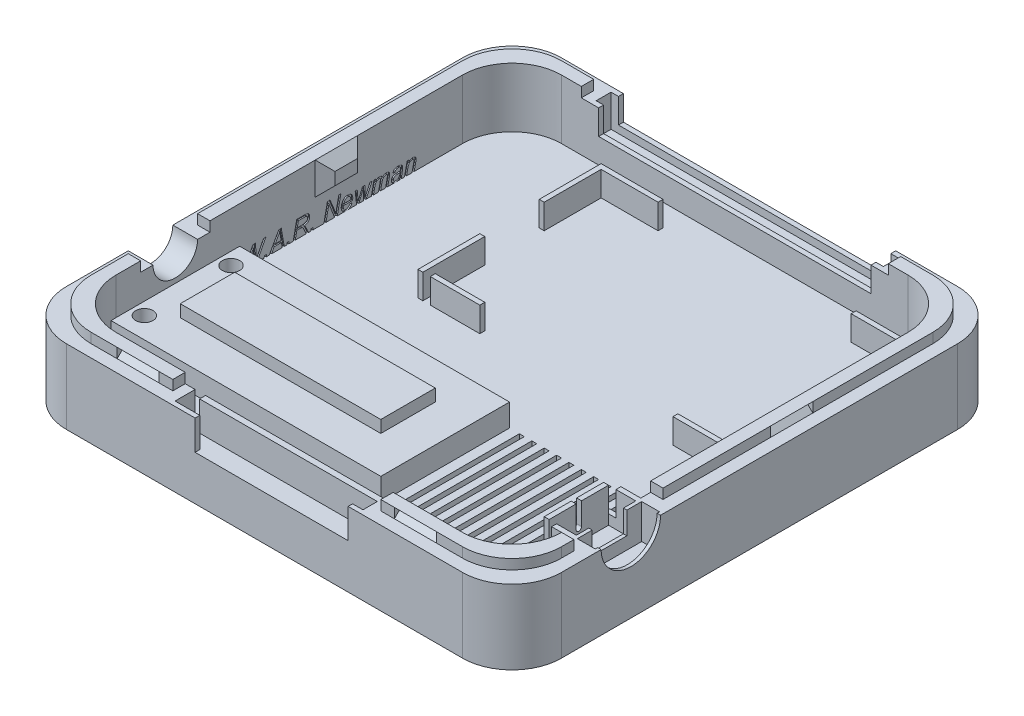
SolidWorks part; units mm, degrees
material "ABS"
ref_plane "Front Plane" through (0, 0, 0) normal (0, 0, 1) x (1, 0, 0)
ref_plane "Top Plane" through (0, 0, 0) normal (0, 1, 0) x (1, 0, 0)
ref_plane "Right Plane" through (0, 0, 0) normal (1, 0, 0) x (0, 0, -1)
sketch "Sketch1" plane through (0, 0, 0) normal (0, 1, 0) x (1, 0, 0)
  line L1 (10, 0) -> (90, 0)
  line L2 (0, 10) -> (0, 90)
  line L3 (10, 100) -> (90, 100)
  line L4 (100, 10) -> (100, 90)
  line L5 (15, 95) -> (85, 95)
  line L6 (5, 85) -> (5, 15)
  line L7 (15, 5) -> (85, 5)
  line L8 (95, 85) -> (95, 15)
  arc A0 (90, 100) -> (100, 90) centre (90, 90) cw
  arc A1 (100, 10) -> (90, 0) centre (90, 10) cw
  arc A2 (10, 0) -> (0, 10) centre (10, 10) cw
  arc A3 (0, 90) -> (10, 100) centre (10, 90) cw
  arc A4 (85, 95) -> (95, 85) centre (85, 85) cw
  arc A5 (95, 15) -> (85, 5) centre (85, 15) cw
  arc A6 (15, 5) -> (5, 15) centre (15, 15) cw
  arc A7 (5, 85) -> (15, 95) centre (15, 85) cw
  point P11 (0, 0)
  dimension "D1" = 10
  dimension "D2" = 10
extrude "Boss-Extrude1" add sketch "Sketch1" along normal blind 15
sketch "Sketch2" plane through (0, 0, 0) normal (0, 1, 0) x (1, 0, 0)
  line L1 (15, 95) -> (85, 95)
  line L2 (5, 85) -> (5, 15)
  line L3 (15, 5) -> (85, 5)
  line L4 (95, 85) -> (95, 15)
  arc A0 (85, 95) -> (95, 85) centre (85, 85) cw
  arc A1 (95, 15) -> (85, 5) centre (85, 15) cw
  arc A2 (15, 5) -> (5, 15) centre (15, 15) cw
  arc A3 (5, 85) -> (15, 95) centre (15, 85) cw
  dimension "D1" = 10
extrude "Boss-Extrude2" add sketch "Sketch2" along normal blind 5
sketch "Sketch5" plane through (0, 0, 0) normal (1, 0, 0) x (0, 0, -1)
  line L0 (15, 15) -> (27, 15)
  line L1 (85, 15) -> (15, 15) construction
  circle A0 centre (27, 15) radius 4.5
extrude "Cut-Extrude2" cut sketch "Sketch5" along normal blind 5 contours A0 region at (0, 10.6273, -27)
ref_plane "Plane1" through (0, 15, 0) normal (0, 1, 0) x (1, 0, 0)
ref_plane "Plane2" through (27.2, 0, 0) normal (1, 0, 0) x (0, 0, -1)
ref_plane "Plane3" through (0, 0, -5) normal (0, 0, 1) x (1, 0, 0)
ref_plane "Plane4" through (10, 0, 0) normal (1, 0, 0) x (0, 0, -1)
ref_plane "Plane5" through (0, 0, -10) normal (0, 0, 1) x (1, 0, 0)
ref_plane "Plane6" through (10, 0, -10) normal (-0.7071, 0, 0.7071) x (0.7071, 0, 0.7071)
ref_plane "Plane7" through (0, 0, -90) normal (0, 0, 1) x (1, 0, 0)
ref_plane "Plane8" through (-40, 0, -40) normal (0.7071, 0, 0.7071) x (0.7071, 0, -0.7071)
ref_plane "Plane9" through (90, 0, 0) normal (1, 0, 0) x (0, 0, -1)
ref_plane "Plane10" through (40, 0, 40) normal (0.7071, 0, 0.7071) x (0.7071, 0, -0.7071)
ref_plane "Plane11" through (90, 0, -90) normal (-0.7071, 0, 0.7071) x (0.7071, 0, 0.7071)
sketch "Sketch21" plane through (0, 0, 0) normal (0, 1, 0) x (1, 0, 0)
  line L0 (5, 27) -> (5, 40)
  line L1 (5, 22.5) -> (5, 31.5) construction
  line L2 (5, 85) -> (5, 15) construction
  line L3 (5, 27) -> (5, 14)
  line L4 (5, 40) -> (59.5, 40)
  line L5 (59.5, 40) -> (59.5, 14)
  line L6 (59.5, 14) -> (5, 14)
extrude "Boss-Extrude3" add sketch "Sketch21" along normal blind 9.55
sketch "Sketch22" plane through (0, 0, 0) normal (0, 1, 0) x (1, 0, 0)
  line L16 (28, 78) -> (28.5, 78)
  line L17 (40, 90) -> (40, 89.5)
  line L18 (40, 90) -> (40, 90.5)
  line L19 (28, 78) -> (27.5, 78)
  line L20 (27.5, 78) -> (27.5, 90.5)
  line L21 (27.5, 90.5) -> (40, 90.5)
  line L22 (40, 89.5) -> (28.5, 89.5)
  line L23 (28.5, 89.5) -> (28.5, 78)
  line L24 (91, 78) -> (90.5, 78)
  line L25 (91, 78) -> (91.5, 78)
  line L26 (79, 90) -> (79, 89.5)
  line L27 (79, 90) -> (79, 90.5)
  line L36 (28.5, 66) -> (28.5, 55.5)
  line L38 (27.5, 66) -> (27.5, 54.5)
  line L40 (90.5, 66) -> (90.5, 55.5)
  line L42 (91.5, 66) -> (91.5, 54.5)
  line L43 (90.5, 54.5) -> (79, 54.5)
  line L44 (79, 90.5) -> (91.5, 90.5)
  line L45 (91.5, 90.5) -> (91.5, 78)
  line L46 (90.5, 78) -> (90.5, 89.5)
  line L47 (90.5, 89.5) -> (79, 89.5)
  line L48 (28.5, 55.5) -> (28.5, 54.5)
  line L52 (30, 54.5) -> (40, 54.5)
  line L53 (27.5, 54.5) -> (27.5, 53.5)
  line L54 (27.5, 53.5) -> (28.5, 53.5)
  line L55 (28.5, 53.5) -> (28.5, 54.5)
  line L56 (30, 53.5) -> (40, 53.5)
  line L57 (27.5, 66) -> (28.5, 66)
  line L58 (40, 53.5) -> (40, 54.5)
  line L59 (79, 54.5) -> (79, 53.5)
  line L60 (30, 54.5) -> (30, 53.5)
  line L61 (79, 53.5) -> (91.5, 53.5)
  line L62 (91.5, 53.5) -> (91.5, 54.5)
  line L63 (90.5, 55.5) -> (90.5, 54.5)
  line L64 (90.5, 66) -> (91.5, 66)
extrude "Boss-Extrude4" add sketch "Sketch22" along normal blind 10
ref_plane "Plane12" through (0, 15, 0) normal (0, 1, 0) x (1, 0, 0)
ref_plane "Plane15" through (96, 0, 0) normal (1, 0, 0) x (0, 0, -1)
sketch "Sketch26" plane through (96, 0, 0) normal (1, 0, 0) x (0, 0, -1)
  line L1 (15, 15) -> (85, 15) construction
  line L2 (18, 15) -> (30, 15)
  line L3 (30, 15) -> (30, 8)
  line L4 (30, 8) -> (18, 8)
  line L5 (18, 8) -> (18, 15)
extrude "Cut-Extrude20" cut sketch "Sketch26" along normal blind 3.3
ref_plane "Plane16" through (100, 0, 0) normal (1, 0, 0) x (0, 0, -1)
sketch "Sketch29" plane through (100, 0, 0) normal (1, 0, 0) x (0, 0, -1)
  line L1 (30, 15) -> (18, 15) construction
  circle A0 centre (24, 15) radius 6
extrude "Cut-Extrude21" cut sketch "Sketch29" against normal blind 1
ref_plane "Plane17" through (95, 0, 0) normal (1, 0, 0) x (0, 0, -1)
sketch "Sketch30" plane through (95, 0, 0) normal (1, 0, 0) x (0, 0, -1)
  line L0 (30, 13) -> (30, 15)
  line L1 (15, 15) -> (85, 15) construction
  line L2 (18, 15) -> (30, 15)
  line L7 (30, 11.5) -> (30, 13)
  line L10 (30.5, 11.5) -> (30, 11.5)
  line L13 (17.5, 13) -> (17.5, 12)
  line L15 (30.5, 15) -> (30, 15)
  line L16 (17.5, 13) -> (17.5, 15)
  line L17 (17.5, 15) -> (18, 15)
  line L19 (30.5, 11.5) -> (30.5, 15)
  line L20 (18, 15) -> (18, 11.5)
  line L21 (18, 11.5) -> (17.5, 11.5)
  line L22 (17.5, 11.5) -> (17.5, 12)
  circle A0 centre (24, 10.3) radius 0.5
extrude "Cut-Extrude23" cut sketch "Sketch30" along normal blind 1.5 contours L15 L0 L7 L10 | L17 L16 L13 | A0 region at (95, 13.25, -17.75) region at (95, 13.25, -30.25)
ref_plane "Plane18" through (0, 15, 0) normal (0, 1, 0) x (1, 0, 0)
sketch "Sketch32" plane through (0, 15, 0) normal (0, 1, 0) x (1, 0, 0)
  line L0 (96, 30) -> (95.7, 30)
  line L1 (96, 30) -> (95, 30) construction
  line L2 (95.7, 30) -> (95.7, 18)
  line L3 (96, 18) -> (95, 18) construction
  line L4 (95.7, 18) -> (96, 18)
  line L5 (96, 18) -> (96, 30)
extrude "Cut-Extrude24" cut sketch "Sketch32" against normal blind 6
sketch "Sketch50" plane through (0, 0, 0) normal (0, 1, 0) x (1, 0, 0)
  line L0 (11.5, 27) -> (11.5, 32.5)
  line L1 (11.5, 32.5) -> (52, 32.5)
  line L3 (11.5, 21.5) -> (52, 21.5)
  line L5 (11.5, 27) -> (11.5, 21.5)
  line L6 (52, 32.5) -> (52, 21.5)
extrude "Boss-Extrude14" add sketch "Sketch50" along normal blind 12
ref_plane "Plane19" through (0, 15, 0) normal (0, 1, 0) x (1, 0, 0)
sketch "Sketch33" plane through (0, 15, 0) normal (0, 1, 0) x (1, 0, 0)
  line L0 (5, 20) -> (5, 15)
  line L1 (96.5, 33) -> (97.5, 33)
  line L3 (96.5, 33) -> (95, 33)
  line L4 (95, 15) -> (95, 85) construction
  line L5 (96.5, 15) -> (95, 15)
  line L6 (96.5, 15) -> (97.5, 15)
  line L9 (2.5, 34) -> (5, 34)
  line L10 (5, 40) -> (5, 15) construction
  line L12 (2.5, 20) -> (5, 20)
  line L13 (12.5, 97.5) -> (87.5, 97.5)
  line L14 (2.5, 87.5) -> (2.5, 34)
  line L15 (12.5, 2.5) -> (87.5, 2.5)
  line L16 (97.5, 87.5) -> (97.5, 33)
  line L17 (15, 95) -> (85, 95)
  line L18 (5, 85) -> (5, 34)
  line L19 (15, 5) -> (85, 5)
  line L20 (95, 85) -> (95, 33)
  line L21 (2.5, 20) -> (2.5, 12.5)
  line L22 (97.5, 15) -> (97.5, 12.5)
  arc A0 (87.5, 97.5) -> (97.5, 87.5) centre (87.5, 87.5) cw
  arc A1 (97.5, 12.5) -> (87.5, 2.5) centre (87.5, 12.5) cw
  arc A2 (12.5, 2.5) -> (2.5, 12.5) centre (12.5, 12.5) cw
  arc A3 (2.5, 87.5) -> (12.5, 97.5) centre (12.5, 87.5) cw
  arc A4 (85, 95) -> (95, 85) centre (85, 85) cw
  arc A5 (95, 15) -> (85, 5) centre (85, 15) cw
  arc A6 (15, 5) -> (5, 15) centre (15, 15) cw
  arc A7 (5, 85) -> (15, 95) centre (15, 85) cw
  dimension "D1" = 10
  dimension "D2" = 10
extrude "Boss-Extrude5" add sketch "Sketch33" along normal blind 2
ref_plane "Plane20" through (0, 17, 0) normal (0, 1, 0) x (1, 0, 0)
sketch "Sketch35" plane through (0, 17, 0) normal (0, 1, 0) x (1, 0, 0)
  line L0 (31, 5) -> (31, 0.95)
  line L1 (15, 5) -> (85, 5) construction
  line L3 (69, 3.8) -> (69, 0.9)
  line L8 (36, 0) -> (66.9, 0)
  line L10 (33.1, 3.8) -> (69, 3.8)
  line L12 (33.1, 5) -> (33.1, 3.8)
  line L13 (31, 5) -> (33.1, 5)
  line L15 (36, 0) -> (36, 0.95)
  line L17 (31, 5) -> (31, 2.5)
  line L21 (12.5, 2.5) -> (87.5, 2.5) construction
  line L23 (69, 2.5) -> (69, 3.8)
  line L24 (36, 0.95) -> (31, 0.95)
  line L25 (66.9, 0) -> (66.9, 0.9)
  line L26 (66.9, 0.9) -> (69, 0.9)
extrude "Cut-Extrude27" cut sketch "Sketch35" against normal blind 8 contours L25 L26 L3 L10 L12 L13 L0 L24 L15 L8 region at (49.9944, 17, -2.0127)
sketch "Sketch36" plane through (0, 17, 0) normal (0, 1, 0) x (1, 0, 0)
  line L0 (31, 2.5) -> (29, 2.5)
  line L1 (12.5, 2.5) -> (31, 2.5) construction
  line L2 (29, 2.5) -> (29, 5)
  line L3 (31, 5) -> (15, 5) construction
  line L4 (69, 2.5) -> (71, 2.5)
  line L5 (69, 2.5) -> (87.5, 2.5) construction
  line L6 (71, 2.5) -> (71, 5)
  line L7 (15, 5) -> (85, 5) construction
  line L8 (71, 5) -> (29, 5)
  line L9 (31, 2.5) -> (69, 2.5)
extrude "Cut-Extrude28" cut sketch "Sketch36" against normal blind 2
sketch "Sketch37" plane through (0, 17, 0) normal (0, 1, 0) x (1, 0, 0)
  line L2 (22.5, 96) -> (77.5, 96)
  line L8 (22.5, 99) -> (77.5, 99)
  line L9 (22.5, 99) -> (21, 99)
  line L10 (21, 99) -> (21, 96)
  line L11 (21, 96) -> (22.5, 96)
  line L12 (77.5, 99) -> (79, 99)
  line L13 (79, 99) -> (79, 96)
  line L14 (79, 96) -> (77.5, 96)
extrude "Cut-Extrude29" cut sketch "Sketch37" against normal blind 8.5
sketch "Sketch38" plane through (0, 17, 0) normal (0, 1, 0) x (1, 0, 0)
  line L0 (77.5, 99) -> (77.5, 100)
  line L1 (90, 100) -> (10, 100) construction
  line L2 (21, 96) -> (79, 96) construction
  line L3 (22.5, 100) -> (22.5, 99)
  line L4 (21, 99) -> (79, 99) construction
  line L5 (77.5, 96) -> (77.5, 95)
  line L6 (85, 95) -> (15, 95) construction
  line L7 (22.5, 96) -> (22.5, 95)
  line L8 (22.5, 100) -> (77.5, 100)
  line L9 (22.5, 95) -> (77.5, 95)
  line L10 (77.5, 99) -> (22.5, 99)
  line L11 (22.5, 96) -> (77.5, 96)
extrude "Cut-Extrude30" cut sketch "Sketch38" against normal blind 7
sketch "Sketch39" plane through (0, 17, 0) normal (0, 1, 0) x (1, 0, 0)
  line L1 (19, 99) -> (19, 100)
  line L2 (22.5, 100) -> (10, 100) construction
  line L3 (19, 100) -> (22.5, 100)
  line L4 (22.5, 100) -> (22.5, 95)
  line L5 (22.5, 95) -> (19, 95)
  line L6 (15, 95) -> (22.5, 95) construction
  line L7 (19, 95) -> (19, 99)
  line L8 (81, 99) -> (81, 100)
  line L9 (90, 100) -> (77.5, 100) construction
  line L10 (81, 100) -> (77.5, 100)
  line L11 (77.5, 100) -> (77.5, 95)
  line L12 (77.5, 95) -> (81, 95)
  line L13 (85, 95) -> (15, 95) construction
  line L14 (81, 95) -> (81, 99)
extrude "Cut-Extrude31" cut sketch "Sketch39" against normal blind 2
ref_plane "Plane21" through (0, 0, -63.25) normal (0, 0, 1) x (1, 0, 0)
sketch "Sketch40" plane through (0, 0, -63.25) normal (0, 0, 1) x (1, 0, 0)
  line L0 (95, 17) -> (93, 15)
  line L1 (93, 15) -> (93, 12.5)
  line L2 (93, 12.5) -> (95, 10.5)
  line L6 (95, 17) -> (95, 5) construction
  line L7 (95, 17) -> (95, 10.5)
  dimension "D1" = 2
extrude "Boss-Extrude7" add sketch "Sketch40" along normal blind 8.5 contours L7 L2 L1 L0
sketch "Sketch41" plane through (0, 0, -63.25) normal (0, 0, 1) x (1, 0, 0)
  line L0 (5, 17) -> (7, 15)
  line L1 (7, 15) -> (7, 12.5)
  line L2 (7, 12.5) -> (5, 10.5)
  line L4 (5, 17) -> (5, 5) construction
  line L5 (5, 10.5) -> (5, 17)
  dimension "D1" = 2
extrude "Boss-Extrude11" add sketch "Sketch41" along normal blind 8 and the other way blind 0.5
sketch "Sketch42" plane through (0, 0, -63.25) normal (0, 0, 1) x (1, 0, 0)
  line L0 (97.5, 17) -> (96.5, 16)
  line L1 (96.5, 16) -> (97.5, 15)
  line L2 (97.5, 17) -> (97.5, 15)
extrude "Cut-Extrude32" cut sketch "Sketch42" along normal blind 8.5
sketch "Sketch43" plane through (0, 0, -63.25) normal (0, 0, 1) x (1, 0, 0)
  line L0 (2.5, 17) -> (3.5, 16)
  line L1 (2.5, 15) -> (3.5, 16)
  line L2 (2.5, 17) -> (2.5, 15)
extrude "Cut-Extrude33" cut sketch "Sketch43" along normal blind 8 and the other way blind 0.5
ref_plane "Plane22" through (78, 0, 0) normal (1, 0, 0) x (0, 0, -1)
sketch "Sketch44" plane through (78, 0, 0) normal (1, 0, 0) x (0, 0, -1)
  line L0 (5, 17) -> (7, 15)
  line L1 (7, 15) -> (7, 12.5)
  line L2 (7, 12.5) -> (5, 10.5)
  line L4 (5, 17) -> (5, 5) construction
  line L5 (5, 10.5) -> (5, 17)
  dimension "D1" = 2
extrude "Boss-Extrude12" add sketch "Sketch44" along normal blind 4.25 and the other way blind 4.25
sketch "Sketch45" plane through (78, 0, 0) normal (1, 0, 0) x (0, 0, -1)
  line L0 (2.5, 17) -> (3.5, 16)
  line L1 (3.5, 16) -> (2.5, 15)
  line L2 (2.5, 17) -> (2.5, 15)
extrude "Cut-Extrude34" cut sketch "Sketch45" against normal blind 4.25 and the other way blind 4.25
ref_plane "Plane23" through (22, 0, 0) normal (1, 0, 0) x (0, 0, -1)
sketch "Sketch46" plane through (22, 0, 0) normal (1, 0, 0) x (0, 0, -1)
  line L0 (5, 17) -> (7, 15)
  line L1 (7, 15) -> (7, 12.5)
  line L2 (7, 12.5) -> (5, 10.5)
  line L3 (5, 17) -> (5, 5) construction
  line L4 (5, 10.5) -> (5, 17)
  dimension "D1" = 2
extrude "Boss-Extrude13" add sketch "Sketch46" along normal blind 4.25 and the other way blind 4.25
sketch "Sketch47" plane through (22, 0, 0) normal (1, 0, 0) x (0, 0, -1)
  line L0 (2.5, 17) -> (3.5, 16)
  line L1 (3.5, 16) -> (2.5, 15)
  line L2 (2.5, 17) -> (2.5, 15)
extrude "Cut-Extrude35" cut sketch "Sketch47" against normal blind 4.25 and the other way blind 4.25
ref_plane "Plane24" through (0, 17, 0) normal (0, 1, 0) x (1, 0, 0)
sketch "Sketch48" plane through (0, 17, 0) normal (0, 1, 0) x (1, 0, 0)
  line L0 (5, 63.75) -> (7, 61.75)
  line L1 (7, 63.75) -> (7, 55.25) construction
  line L2 (5, 55.25) -> (7, 57.25)
  line L3 (17.75, 5) -> (19.75, 7)
  line L4 (17.75, 7) -> (26.25, 7) construction
  line L5 (26.25, 5) -> (24.25, 7)
  line L6 (82.25, 5) -> (80.25, 7)
  line L7 (73.75, 7) -> (82.25, 7) construction
  line L8 (73.75, 5) -> (75.75, 7)
  line L9 (95, 63.25) -> (93, 61.25)
  line L10 (93, 54.75) -> (93, 63.25) construction
  line L11 (95, 54.75) -> (93, 56.75)
  line L12 (93, 56.75) -> (93, 54.75)
  line L13 (95, 54.75) -> (93, 54.75) construction
  line L14 (93, 54.75) -> (95, 54.75)
  line L15 (95, 63.25) -> (93, 63.25)
  line L16 (93, 63.25) -> (93, 61.25)
  line L17 (5, 63.75) -> (7, 63.75)
  line L18 (7, 63.75) -> (7, 61.75)
  line L19 (7, 57.25) -> (7, 55.25)
  line L20 (7, 55.25) -> (5, 55.25)
  line L21 (19.75, 7) -> (17.75, 7)
  line L22 (17.75, 7) -> (17.75, 5)
  line L23 (24.25, 7) -> (26.25, 7)
  line L24 (26.25, 7) -> (26.25, 5)
  line L25 (80.25, 7) -> (82.25, 7)
  line L26 (82.25, 7) -> (82.25, 5)
  line L27 (75.75, 7) -> (73.75, 7)
  line L28 (73.75, 7) -> (73.75, 5)
extrude "Cut-Extrude36" cut sketch "Sketch48" against normal blind 10
sketch "Sketch49" plane through (0, 15, 0) normal (0, 1, 0) x (1, 0, 0)
  line L1 (95, 18) -> (95, 30) construction
  line L3 (95.7, 30) -> (95.7, 18) construction
  line L6 (95, 24) -> (95, 24.5)
  line L7 (95, 24.5) -> (95.7, 24.5)
  line L8 (95.7, 24.5) -> (95.7, 24)
  line L9 (95.7, 24) -> (95.7, 23.5)
  line L10 (95.7, 23.5) -> (95, 23.5)
  line L11 (95, 23.5) -> (95, 24)
extrude "Cut-Extrude37" cut sketch "Sketch49" against normal blind 4.7
sketch "Sketch51" plane through (0, 0, 0) normal (0, 1, 0) x (1, 0, 0)
  line L0 (95, 30.5) -> (89.5, 30.5)
  line L1 (96.5, 17.5) -> (89.5, 17.5)
  line L2 (89, 18) -> (89, 30)
  line L3 (95, 30.5) -> (96.5, 30.5)
  line L4 (96.5, 30.5) -> (96.5, 30)
  line L5 (96.5, 30.5) -> (96.5, 30) construction
  line L6 (96.5, 30.5) -> (96.5, 30) construction
  line L7 (96.5, 30) -> (95, 30)
  line L8 (95, 30) -> (89.5, 30)
  line L9 (96.5, 17.5) -> (96.5, 18)
  line L10 (96.5, 18) -> (95, 18)
  line L11 (95, 15) -> (95, 85) construction
  line L12 (95, 18) -> (89.5, 18)
  line L13 (89.5, 18) -> (89.5, 30)
  arc A0 (89.5, 17.5) -> (89, 18) centre (89.5, 18) cw
  arc A1 (89, 30) -> (89.5, 30.5) centre (89.5, 30) cw
  dimension "D1" = 0.5
extrude "Boss-Extrude15" add sketch "Sketch51" along normal blind 15
sketch "Sketch52" plane through (0, 15, 0) normal (0, 1, 0) x (1, 0, 0)
  line L0 (95.7, 30) -> (96, 30)
  line L1 (96, 30) -> (96, 18)
  line L2 (96, 18) -> (95.7, 18)
  line L3 (95.7, 18) -> (95.7, 30)
extrude "Cut-Extrude38" cut sketch "Sketch52" against normal blind 7
sketch "Sketch53" plane through (0, 0, 0) normal (0, 1, 0) x (1, 0, 0)
  line L0 (89.5, 30) -> (95, 30)
  line L1 (95, 30) -> (95, 18)
  line L2 (95, 18) -> (89.5, 18)
  line L3 (89.5, 18) -> (89.5, 30)
extrude "Boss-Extrude16" add sketch "Sketch53" along normal blind 8
sketch "Sketch54" plane through (0, 15, 0) normal (0, 1, 0) x (1, 0, 0)
  line L0 (95, 24) -> (95, 26)
  line L1 (95, 18) -> (95, 30) construction
  line L2 (95, 26) -> (95.7, 26)
  line L3 (95.7, 30) -> (95.7, 18) construction
  line L4 (95.7, 26) -> (95.7, 22)
  line L5 (95.7, 22) -> (95, 22)
  line L6 (95, 18) -> (95, 23.5) construction
  line L7 (95, 22) -> (95, 24)
extrude "Cut-Extrude39" cut sketch "Sketch54" against normal blind 4.5
sketch "Sketch55" plane through (0, 0, 0) normal (0, 1, 0) x (1, 0, 0)
  line L0 (95, 24.5) -> (95.7, 24.5)
  line L1 (95.7, 24.5) -> (95.7, 23.5)
  line L2 (95.7, 23.5) -> (95, 23.5)
  line L3 (95, 23.5) -> (95, 24.5)
extrude "Boss-Extrude17" add sketch "Sketch55" along normal blind 10.5
ref_plane "Plane25" through (89, 0, 0) normal (1, 0, 0) x (0, 0, -1)
sketch "Sketch56" plane through (89, 0, 0) normal (1, 0, 0) x (0, 0, -1)
  line L0 (18, 15) -> (17.5, 15)
  line L1 (30, 15) -> (18, 15) construction
  line L2 (23.45, 10.5) -> (23.45, 15)
  line L3 (23.45, 15) -> (24.55, 15)
  line L4 (24.55, 15) -> (24.55, 10.5)
  line L5 (17.5, 15) -> (17.5, 10)
  line L6 (17.5, 5) -> (17.5, 15) construction
  line L7 (17.5, 10) -> (18, 10)
  line L8 (18, 15) -> (18, 5) construction
  line L9 (18, 10) -> (18, 15)
  line L10 (30.5, 15) -> (30, 15)
  line L11 (30, 15) -> (30, 10)
  line L12 (30, 15) -> (30, 5) construction
  line L13 (30, 10) -> (30.5, 10)
  line L14 (30.5, 5) -> (30.5, 15) construction
  line L15 (30.5, 10) -> (30.5, 15)
  arc A0 (23.45, 10.5) -> (24.55, 10.5) centre (24, 10.5) ccw
extrude "Cut-Extrude40" cut sketch "Sketch56" along normal blind 2
sketch "Sketch57" plane through (0, 0, 0) normal (0, 1, 0) x (1, 0, 0)
  line L0 (95, 30.5) -> (95, 31)
  line L1 (95, 30.5) -> (95, 33) construction
  line L2 (95, 31) -> (89, 31)
  line L3 (95, 17.5) -> (95, 17)
  line L4 (95, 15) -> (95, 17.5) construction
  line L5 (95, 17) -> (89, 17)
  line L6 (88.5, 17.5) -> (88.5, 30.5)
  line L7 (95, 17.5) -> (89.5, 17.5)
  line L8 (89, 18) -> (89, 30)
  line L9 (89.5, 30.5) -> (95, 30.5)
  arc A0 (89.5, 17.5) -> (89, 18) centre (89.5, 18) cw
  arc A1 (88.5, 17.5) -> (89, 17) centre (89, 17.5) ccw
  arc A2 (88.5, 30.5) -> (89, 31) centre (89, 30.5) cw
  arc A3 (89.5, 30.5) -> (89, 30) centre (89.5, 30) ccw
  dimension "D1" = 0.5
extrude "Boss-Extrude18" add sketch "Sketch57" along normal blind 15
sketch "Sketch58" plane through (89, 0, 0) normal (1, 0, 0) x (0, 0, -1)
  line L0 (31, 15) -> (30, 15)
  line L2 (30.5, 15) -> (17.5, 15) construction
  line L5 (30, 15) -> (30, 10)
  line L6 (30, 10) -> (31, 10)
  line L7 (31, 15) -> (31, 5) construction
  line L8 (31, 10) -> (31, 15)
  line L9 (17, 15) -> (18, 15)
  line L10 (18, 15) -> (18, 10)
  line L11 (18, 10) -> (17, 10)
  line L12 (17, 15) -> (17, 5) construction
  line L13 (17, 10) -> (17, 15)
  line L14 (24, 15) -> (23.45, 15)
  line L15 (23.45, 15) -> (24.55, 15) construction
  line L16 (23.45, 10.5) -> (23.45, 15)
  line L17 (24.55, 10.5) -> (24.55, 15)
  line L18 (24, 15) -> (24.55, 15)
  arc A1 (23.45, 10.5) -> (24.55, 10.5) centre (24, 10.5) ccw
extrude "Cut-Extrude42" cut sketch "Sketch58" against normal blind 2 and the other way blind 2
ref_plane "Plane26" through (0, 17, 0) normal (0, 1, 0) x (1, 0, 0)
sketch "Sketch59" plane through (0, 17, 0) normal (0, 1, 0) x (1, 0, 0)
  line L0 (95.7, 30) -> (95.7, 30.5)
  line L1 (95.7, 30.5) -> (99.3, 30.5)
  line L2 (99.3, 30.5) -> (99.3, 30)
  line L3 (99.3, 30) -> (95.7, 30)
  line L4 (95.7, 18) -> (95.7, 17.5)
  line L5 (95.7, 17.5) -> (99.3, 17.5)
  line L6 (99.3, 17.5) -> (99.3, 18)
  line L7 (99.3, 18) -> (95.7, 18)
extrude "Cut-Extrude43" cut sketch "Sketch59" against normal up to vertex (9 mm away) up to point (99.3, 8, -30)
sketch "Sketch60" plane through (0, 0, 0) normal (0, 1, 0) x (1, 0, 0)
  line L0 (61.5, 40) -> (62.5, 40)
  line L1 (61.5, 40) -> (86.5, 40)
  line L3 (61.5, 14) -> (86.5, 14)
  line L5 (62.5, 40) -> (64, 40)
  line L6 (61.5, 40) -> (61.5, 14)
  line L7 (86.5, 40) -> (86.5, 14)
  line L8 (64, 40) -> (65, 40)
  line L9 (65, 40) -> (66.5, 40)
  line L10 (66.5, 40) -> (67.5, 40)
  line L11 (67.5, 40) -> (69, 40)
  line L12 (69, 40) -> (70, 40)
  line L13 (70, 40) -> (71.5, 40)
  line L14 (71.5, 40) -> (72.5, 40)
  line L15 (72.5, 40) -> (74, 40)
  line L16 (74, 40) -> (75, 40)
  line L17 (75, 40) -> (76.5, 40)
  line L18 (76.5, 40) -> (77.5, 40)
  line L19 (77.5, 40) -> (79, 40)
  line L20 (79, 40) -> (80, 40)
  line L21 (80, 40) -> (81.5, 40)
  line L22 (81.5, 40) -> (82.5, 40)
  line L23 (82.5, 40) -> (84, 40)
  line L24 (84, 40) -> (85, 40)
  line L25 (85, 40) -> (86.5, 40)
  line L26 (62.5, 40) -> (62.5, 14)
  line L27 (64, 40) -> (64, 14)
  line L28 (65, 40) -> (65, 14)
  line L29 (66.5, 40) -> (66.5, 14)
  line L30 (67.5, 40) -> (67.5, 14)
  line L31 (69, 40) -> (69, 14)
  line L32 (70, 40) -> (70, 14)
  line L33 (71.5, 40) -> (71.5, 14)
  line L34 (72.5, 40) -> (72.5, 14)
  line L35 (74, 40) -> (74, 14)
  line L36 (75, 40) -> (75, 14)
  line L37 (76.5, 40) -> (76.5, 14)
  line L38 (77.5, 40) -> (77.5, 14)
  line L39 (79, 40) -> (79, 14)
  line L40 (80, 40) -> (80, 14)
  line L41 (81.5, 40) -> (81.5, 14)
  line L42 (82.5, 40) -> (82.5, 14)
  line L43 (84, 40) -> (84, 14)
  line L44 (85, 40) -> (85, 14)
extrude "Cut-Extrude44" cut sketch "Sketch60" along normal blind 10 contours L26 L0 L6 L3 | L28 L1 L27 L3 | L30 L1 L29 L3 | L32 L1 L31 L3 | L34 L1 L33 L3 | L36 L1 L35 L3 | L38 L1 L37 L3 | L40 L1 L39 L3 | L42 L1 L41 L3 | L44 L1 L43 L3 region at (62, 0, -27) region at (64.5, 0, -27) region at (67, 0, -27) region at (69.5, 0, -27) region at (72, 0, -27) region at (74.5, 0, -27) region at (77, 0, -27) region at (79.5, 0, -27) region at (82, 0, -27) region at (84.5, 0, -27)
sketch "Sketch63" plane through (0, 17, 0) normal (0, 1, 0) x (1, 0, 0)
  line L0 (95, 26) -> (95, 27.5)
  line L1 (95, 26) -> (95, 30) construction
  line L2 (95, 27.5) -> (95.7, 27.5)
  line L3 (95.7, 30.5) -> (95.7, 17.5) construction
  line L4 (95.7, 27.5) -> (95.7, 26)
  line L5 (95.7, 30.5) -> (95.7, 26) construction
  line L6 (95.7, 26) -> (95, 26)
  line L7 (95, 22) -> (95.7, 22)
  line L8 (95.7, 22) -> (95.7, 20.5)
  line L9 (95.7, 20.5) -> (95, 20.5)
  line L10 (95, 18) -> (95, 22) construction
  line L11 (95, 20.5) -> (95, 22)
extrude "Cut-Extrude46" cut sketch "Sketch63" against normal blind 6.5
ref_plane "Plane27" through (0, 10, 0) normal (0, 1, 0) x (1, 0, 0)
sketch "Sketch64" plane through (0, 10, 0) normal (0, 1, 0) x (1, 0, 0)
  line L0 (5, 22.5) -> (5, 18.25)
  line L1 (5, 40) -> (5, 15) construction
  line L2 (5, 18.25) -> (7.5, 18.25)
  line L3 (7.5, 18.25) -> (7.5, 35.75)
  line L4 (7.5, 35.75) -> (5, 35.75)
  line L5 (5, 34) -> (5, 55.25) construction
  line L6 (5, 35.75) -> (5, 31.5)
  circle A0 centre (7.5, 35.75) radius 1.75
  circle A1 centre (7.5, 18.25) radius 1.75
extrude "Cut-Extrude47" cut sketch "Sketch64" against normal blind 5 contours L3 A0 L4 | L3 A1 L2 | L2 A1 L3 | L4 A0 L3 region at (6.7573, 10, -18.9927) region at (6.7573, 10, -35.0073) region at (7.7476, 10, -35.9976) region at (7.7476, 10, -18.0024)
ref_plane "Plane28" through (5, 0, 0) normal (1, 0, 0) x (0, 0, -1)
sketch "Sketch65" plane through (5, 0, 0) normal (1, 0, 0) x (0, 0, -1)
  text T0 "<i>W.A.R. Newman</i>"
extrude "Cut-Extrude48" cut sketch "Sketch65" against normal blind 0.25
